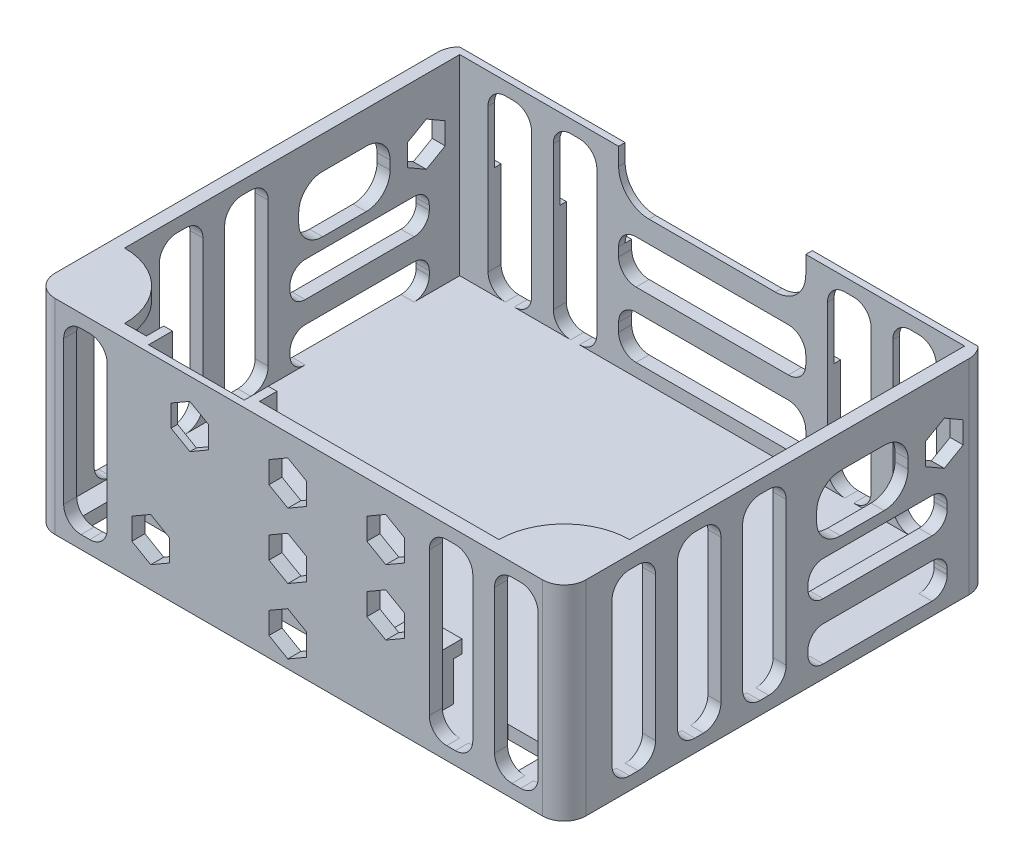
SolidWorks part; units mm, degrees
ref_plane "Front Plane" through (0, 0, 0) normal (0, 0, 1) x (1, 0, 0)
ref_plane "Top Plane" through (0, 0, 0) normal (0, 1, 0) x (1, 0, 0)
ref_plane "Right Plane" through (0, 0, 0) normal (1, 0, 0) x (0, 0, -1)
sketch "Sketch1" plane through (0, 0, 0) normal (0, 1, 0) x (1, 0, 0)
  line L1 (-81.2987, -43.7828) -> (-20.2987, -43.7828)
  line L2 (-81.2987, -43.7828) -> (-81.2987, 5.2172)
  line L3 (-81.2987, 5.2172) -> (-20.2987, 5.2172)
  line L4 (-20.2987, -43.7828) -> (-20.2987, 5.2172)
  dimension "D1" = 61
  dimension "D2" = 49
extrude "Boss-Extrude1" add sketch "Sketch1" along normal blind 23.5
sketch "Sketch2" plane through (0, 23.5, 0) normal (0, 1, 0) x (1, 0, 0)
  line L0 (-81.2987, 5.2172) -> (-81.2987, -43.7828) construction
  line L1 (-79.7987, 3.7172) -> (-21.7987, 3.7172)
  line L2 (-79.7987, 3.7172) -> (-79.7987, -42.2828)
  line L3 (-79.7987, -42.2828) -> (-21.7987, -42.2828)
  line L4 (-21.7987, 3.7172) -> (-21.7987, -42.2828)
  line L5 (-81.2987, -43.7828) -> (-20.2987, -43.7828) construction
  line L6 (-20.2987, -43.7828) -> (-20.2987, 5.2172) construction
  line L7 (-20.2987, 5.2172) -> (-81.2987, 5.2172) construction
  dimension "D1" = 1.5
  dimension "D2" = 1.5
  dimension "D3" = 1.5
  dimension "D4" = 1.5
extrude "Cut-Extrude1" cut sketch "Sketch2" against normal blind 22
sketch "Sketch3" plane through (0, 1.5, 0) normal (0, 1, 0) x (1, 0, 0)
  line L0 (-79.7987, -42.2828) -> (-21.7987, -42.2828) construction
  line L1 (-58.5387, -39.2828) -> (-42.5387, -39.2828)
  line L2 (-58.5387, -39.2828) -> (-58.5387, -42.2828)
  line L3 (-58.5387, -42.2828) -> (-42.5387, -42.2828)
  line L4 (-42.5387, -39.2828) -> (-42.5387, -42.2828)
  line L5 (-21.7987, -42.2828) -> (-21.7987, 3.7172) construction
  line L6 (-32.3987, -38.1328) -> (-27.1987, -38.1328)
  line L7 (-32.3987, -38.1328) -> (-32.3987, -42.2828)
  line L8 (-32.3987, -42.2828) -> (-27.1987, -42.2828)
  line L9 (-27.1987, -38.1328) -> (-27.1987, -42.2828)
  line L10 (-65.5387, -37.2828) -> (-77.5387, -37.2828)
  line L11 (-65.5387, -37.2828) -> (-65.5387, -42.2828)
  line L12 (-65.5387, -42.2828) -> (-77.5387, -42.2828)
  line L13 (-77.5387, -37.2828) -> (-77.5387, -42.2828)
  dimension "D1" = 3
  dimension "D2" = 5.4
  dimension "D3" = 5.2
  dimension "D4" = 10.14
  dimension "D5" = 4.15
  dimension "D6" = 7
  dimension "D7" = 12
  dimension "D8" = 16
  dimension "D9" = 5
extrude "Cut-Extrude2" cut sketch "Sketch3" against normal blind 1.5
sketch "Sketch4" plane through (0, 23.5, 0) normal (0, 1, 0) x (1, 0, 0)
  line L0 (-20.2987, 5.2172) -> (-81.2987, 5.2172) construction
  line L1 (-61.5487, 5.2172) -> (-40.0487, 5.2172)
  line L2 (-61.5487, 5.2172) -> (-61.5487, 3.7172)
  line L3 (-61.5487, 3.7172) -> (-40.0487, 3.7172)
  line L4 (-40.0487, 5.2172) -> (-40.0487, 3.7172)
  line L5 (-21.7987, 3.7172) -> (-79.7987, 3.7172) construction
  dimension "D1" = 18.25
  dimension "D2" = 18.25
extrude "Cut-Extrude3" cut sketch "Sketch4" against normal blind 5.5
sketch "Sketch5" plane through (-81.2987, 0, 0) normal (-1, 0, 0) x (0, 0, 1)
  line L0 (-5.2172, 23.5) -> (43.7828, 23.5) construction
  line L1 (4.2828, 19.75) -> (14.7828, 19.75)
  line L2 (4.2828, 19.75) -> (4.2828, 13.25)
  line L3 (4.2828, 13.25) -> (14.7828, 13.25)
  line L4 (14.7828, 19.75) -> (14.7828, 13.25)
  dimension "D1" = 10.5
  dimension "D2" = 6.5
  dimension "D3" = 3.75
  dimension "D4" = 8
extrude "Cut-Extrude6" cut sketch "Sketch5" against normal blind 61
sketch "Sketch8" plane through (0, 1.5, 0) normal (0, 1, 0) x (1, 0, 0)
  line L0 (-42.5387, -42.2828) -> (-32.3987, -42.2828) construction
  line L1 (-37.5387, -42.2828) -> (-42.5387, -42.2828)
  line L2 (-37.5387, -42.2828) -> (-37.5387, -39.2828)
  line L3 (-37.5387, -39.2828) -> (-42.5387, -39.2828)
  line L4 (-42.5387, -42.2828) -> (-42.5387, -39.2828)
  line L6 (-58.5387, -42.2828) -> (-63.5387, -42.2828)
  line L7 (-58.5387, -42.2828) -> (-58.5387, -39.2828)
  line L8 (-58.5387, -39.2828) -> (-63.5387, -39.2828)
  line L9 (-63.5387, -42.2828) -> (-63.5387, -39.2828)
  dimension "D1" = 5
  dimension "D2" = 5
extrude "Boss-Extrude2" add sketch "Sketch8" along normal blind 6
sketch "Sketch9" plane through (0, 0, 39.2828) normal (0, 0, -1) x (-1, 0, 0)
  line L0 (37.5387, 7.5) -> (42.5387, 7.5) construction
  line L1 (37.5387, 7.5) -> (42.5387, 7.5)
  line L2 (37.5387, 7.5) -> (37.5387, 6)
  line L3 (37.5387, 6) -> (42.5387, 6)
  line L4 (42.5387, 7.5) -> (42.5387, 6)
  line L5 (42.5387, 7.5) -> (42.5387, 1.5) construction
  line L6 (58.5387, 7.5) -> (63.5387, 7.5) construction
  line L7 (58.5387, 7.5) -> (63.5387, 7.5)
  line L8 (58.5387, 7.5) -> (58.5387, 6)
  line L9 (58.5387, 6) -> (63.5387, 6)
  line L10 (63.5387, 7.5) -> (63.5387, 6)
  line L11 (63.5387, 7.5) -> (63.5387, 1.5) construction
  dimension "D1" = 1.5
  dimension "D2" = 1.5
extrude "Boss-Extrude3" add sketch "Sketch9" along normal blind 1
sketch "Sketch10" plane through (0, 0, 42.2828) normal (0, 0, -1) x (-1, 0, 0)
  line L0 (79.7987, 23.5) -> (21.7987, 23.5) construction
  line L1 (57.7987, 23.5) -> (68.7987, 23.5)
  line L2 (57.7987, 23.5) -> (57.7987, 12.5)
  line L3 (57.7987, 12.5) -> (68.7987, 12.5)
  line L4 (68.7987, 23.5) -> (68.7987, 12.5)
  line L5 (79.7987, 1.5) -> (79.7987, 23.5) construction
  dimension "D1" = 11
  dimension "D2" = 11
  dimension "D3" = 0
  dimension "D4" = 11
extrude "Cut-Extrude8" cut sketch "Sketch10" against normal blind 0.75
sketch "Sketch11" plane through (0, 0, 42.2828) normal (0, 0, -1) x (-1, 0, 0)
  line L1 (57.7987, 23.5) -> (56.7987, 23.5)
  line L2 (57.7987, 23.5) -> (57.7987, 11.5)
  line L3 (57.7987, 11.5) -> (56.7987, 11.5)
  line L4 (56.7987, 23.5) -> (56.7987, 11.5)
  line L5 (68.7987, 12.5) -> (57.7987, 12.5)
  line L6 (68.7987, 12.5) -> (68.7987, 11.5)
  line L7 (68.7987, 11.5) -> (57.7987, 11.5)
  line L8 (57.7987, 12.5) -> (57.7987, 11.5)
  line L9 (68.7987, 23.5) -> (69.7987, 23.5)
  line L10 (68.7987, 23.5) -> (68.7987, 11.5)
  line L11 (68.7987, 11.5) -> (69.7987, 11.5)
  line L12 (69.7987, 23.5) -> (69.7987, 11.5)
  line M8 (68.7987, 12.5) -> (57.7987, 12.5)
  line M30 (79.7987, 23.5) -> (68.7987, 23.5)
  line M31 (68.7987, 23.5) -> (68.7987, 12.5)
  dimension "D1" = 1
  dimension "D2" = 1
  dimension "D3" = 1
  dimension "D4" = 0
extrude "Boss-Extrude4" add sketch "Sketch11" along normal blind 2 contours L7 L6 L2 M8 | L12 L6 L11 M30 M31
sketch "Sketch12" plane through (0, 23.5, 0) normal (0, 1, 0) x (1, 0, 0)
  line L1 (-21.7987, -42.2828) -> (-29.2987, -42.2828)
  line L2 (-21.7987, -42.2828) -> (-21.7987, -34.7828)
  line L3 (-21.7987, -34.7828) -> (-29.2987, -34.7828)
  line L4 (-29.2987, -42.2828) -> (-29.2987, -34.7828)
  line L5 (-79.7987, -42.2828) -> (-72.2987, -42.2828)
  line L6 (-79.7987, -42.2828) -> (-79.7987, -34.7828)
  line L7 (-79.7987, -34.7828) -> (-72.2987, -34.7828)
  line L8 (-72.2987, -42.2828) -> (-72.2987, -34.7828)
  dimension "D1" = 7.5
  dimension "D2" = 7.5
  dimension "D3" = 7.5
  dimension "D4" = 7.5
extrude "Boss-Extrude5" add sketch "Sketch12" against normal blind 1.5
fillet "Fillet1" radius 2.75 1 edges at (-80.5487, 13.25, 14.7828)
fillet "Fillet2" radius 2.75 1 edges at (-80.5487, 19.75, 14.7828)
fillet "Fillet3" radius 2.75 1 edges at (-80.5487, 19.75, 4.2828)
fillet "Fillet4" radius 2.75 1 edges at (-80.5487, 13.25, 4.2828)
fillet "Fillet5" radius 3.5 1 edges at (-40.0487, 18, -4.4672)
fillet "Fillet6" radius 3.5 1 edges at (-61.5487, 18, -4.4672)
fillet "Fillet7" radius 7.5 5 edges at (-29.2987, 22, 38.5328) (-25.5487, 22, 34.7828) (-29.2987, 22.75, 34.7828) (-25.5487, 23.5, 34.7828) (-29.2987, 23.5, 38.5328)
fillet "Fillet8" radius 7.5 5 edges at (-76.0487, 22, 34.7828) (-72.2987, 22, 38.5328) (-72.2987, 22.75, 34.7828) (-72.2987, 23.5, 38.5328) (-76.0487, 23.5, 34.7828)
fillet "Fillet9" radius 2.5 1 edges at (-20.2987, 11.75, -5.2172)
fillet "Fillet10" radius 2.5 1 edges at (-81.2987, 11.75, -5.2172)
fillet "Fillet11" radius 2.5 1 edges at (-81.2987, 11.75, 43.7828)
fillet "Fillet12" radius 2.5 1 edges at (-20.2987, 11.75, 43.7828)
sketch "Sketch13" plane through (-20.2987, 0, 0) normal (1, 0, 0) x (0, 0, -1)
  line L0 (-41.2828, 23.5) -> (2.7172, 23.5) construction
  line L1 (-36.2828, 22) -> (-35.2828, 22)
  line L2 (-38.2828, 20) -> (-38.2828, 3.5)
  line L3 (-36.2828, 1.5) -> (-35.2828, 1.5)
  line L4 (-33.2828, 20) -> (-33.2828, 3.5)
  line L5 (-28.7828, 22) -> (-27.7828, 22)
  line L6 (-30.7828, 20) -> (-30.7828, 3.5)
  line L7 (-28.7828, 1.5) -> (-27.7828, 1.5)
  line L8 (-25.7828, 20) -> (-25.7828, 3.5)
  line L9 (-21.2828, 22) -> (-20.2828, 22)
  line L10 (-23.2828, 20) -> (-23.2828, 3.5)
  line L11 (-21.2828, 1.5) -> (-20.2828, 1.5)
  line L12 (-18.2828, 20) -> (-18.2828, 3.5)
  line L17 (-41.2828, 0) -> (2.7172, 0) construction
  line L18 (-38.2828, 7.5) -> (-38.2828, 6) construction
  arc A0 (-36.2828, 22) -> (-38.2828, 20) centre (-36.2828, 20) ccw
  arc A1 (-35.2828, 22) -> (-33.2828, 20) centre (-35.2828, 20) cw
  arc A2 (-28.7828, 22) -> (-30.7828, 20) centre (-28.7828, 20) ccw
  arc A3 (-27.7828, 22) -> (-25.7828, 20) centre (-27.7828, 20) cw
  arc A4 (-21.2828, 22) -> (-23.2828, 20) centre (-21.2828, 20) ccw
  arc A5 (-20.2828, 22) -> (-18.2828, 20) centre (-20.2828, 20) cw
  arc A6 (-20.2828, 1.5) -> (-18.2828, 3.5) centre (-20.2828, 3.5) ccw
  arc A7 (-23.2828, 3.5) -> (-21.2828, 1.5) centre (-21.2828, 3.5) ccw
  arc A8 (-27.7828, 1.5) -> (-25.7828, 3.5) centre (-27.7828, 3.5) ccw
  arc A9 (-30.7828, 3.5) -> (-28.7828, 1.5) centre (-28.7828, 3.5) ccw
  arc A10 (-35.2828, 1.5) -> (-33.2828, 3.5) centre (-35.2828, 3.5) ccw
  arc A11 (-38.2828, 3.5) -> (-36.2828, 1.5) centre (-36.2828, 3.5) ccw
  point P14 (-38.2828, 22)
  point P23 (-33.2828, 22)
  point P26 (-30.7828, 22)
  point P29 (-25.7828, 22)
  point P32 (-23.2828, 22)
  point P35 (-18.2828, 22)
  dimension "D4" = 2
  dimension "D1" = 5
  dimension "D2" = 5
  dimension "D3" = 5
  dimension "D5" = 2.5
  dimension "D6" = 2.5
  dimension "D8" = 1.5
  dimension "D9" = 1.5
  dimension "D10" = 1.5
  dimension "D12" = 1.5
  dimension "D13" = 1.5
  dimension "D14" = 1.5
  dimension "D16" = 0
extrude "Cut-Extrude10" cut sketch "Sketch13" against normal blind 61
fillet "Fillet13" radius 2.75 1 edges at (-21.0487, 13.25, 14.7828)
fillet "Fillet14" radius 2.75 1 edges at (-21.0487, 19.75, 14.7828)
fillet "Fillet15" radius 2.75 1 edges at (-21.0487, 13.25, 4.2828)
fillet "Fillet16" radius 2.75 1 edges at (-21.0487, 19.75, 4.2828)
sketch "Sketch16" plane through (-20.2987, 0, 0) normal (1, 0, 0) x (0, 0, -1)
  line L0 (-4.2828, 17) -> (-4.2828, 16) construction
  line L1 (-0.1178, 19) -> (-2.2828, 17.75)
  line L2 (-2.2828, 17.75) -> (-2.2828, 15.25)
  line L3 (-2.2828, 15.25) -> (-0.1178, 14)
  line L4 (-0.1178, 14) -> (2.0473, 15.25)
  line L5 (2.0473, 15.25) -> (2.0473, 17.75)
  line L6 (2.0473, 17.75) -> (-0.1178, 19)
  circle A0 centre (-0.1178, 16.5) radius 2.1651 construction
  point P10 (-4.2828, 16.5)
  dimension "D1" = 0
  dimension "D2" = 2.5
  dimension "D3" = 2
extrude "Cut-Extrude11" cut sketch "Sketch16" against normal blind 61
sketch "Sketch19" plane through (0, 0, -5.2172) normal (0, 0, -1) x (-1, 0, 0)
  line L0 (61.5487, 23.5) -> (78.7987, 23.5) construction
  line L1 (66.0487, 22) -> (67.0487, 22)
  line L2 (64.0487, 20) -> (64.0487, 3.5)
  line L3 (66.0487, 1.5) -> (67.0487, 1.5)
  line L4 (69.0487, 20) -> (69.0487, 3.5)
  line L5 (73.5487, 22) -> (74.5487, 22)
  line L6 (71.5487, 20) -> (71.5487, 3.5)
  line L7 (73.5487, 1.5) -> (74.5487, 1.5)
  line L8 (76.5487, 20) -> (76.5487, 3.5)
  line L9 (27.0487, 22) -> (28.0487, 22)
  line L10 (25.0487, 20) -> (25.0487, 3.5)
  line L11 (27.0487, 1.5) -> (28.0487, 1.5)
  line L12 (30.0487, 20) -> (30.0487, 3.5)
  line L13 (34.5487, 22) -> (35.5487, 22)
  line L14 (32.5487, 20) -> (32.5487, 3.5)
  line L15 (34.5487, 1.5) -> (35.5487, 1.5)
  line L16 (37.5487, 20) -> (37.5487, 3.5)
  line L17 (42.0487, 15.5) -> (59.5487, 15.5)
  line L18 (40.0487, 13.5) -> (40.0487, 12.5)
  line L19 (42.0487, 10.5) -> (59.5487, 10.5)
  line L20 (61.5487, 13.5) -> (61.5487, 12.5)
  line L21 (42.0487, 8) -> (59.5487, 8)
  line L22 (40.0487, 6) -> (40.0487, 5)
  line L23 (42.0487, 3) -> (59.5487, 3)
  line L24 (61.5487, 6) -> (61.5487, 5)
  line L25 (22.7987, 0) -> (78.7987, 0) construction
  line L26 (61.5487, 21.5) -> (61.5487, 23.5) construction
  line L27 (40.0487, 21.5) -> (40.0487, 23.5) construction
  line L28 (22.7987, 23.5) -> (40.0487, 23.5) construction
  line L29 (43.5487, 18) -> (58.0487, 18) construction
  arc A0 (25.0487, 3.5) -> (27.0487, 1.5) centre (27.0487, 3.5) ccw
  arc A1 (28.0487, 1.5) -> (30.0487, 3.5) centre (28.0487, 3.5) ccw
  arc A2 (32.5487, 3.5) -> (34.5487, 1.5) centre (34.5487, 3.5) ccw
  arc A3 (35.5487, 1.5) -> (37.5487, 3.5) centre (35.5487, 3.5) ccw
  arc A4 (42.0487, 8) -> (40.0487, 6) centre (42.0487, 6) ccw
  arc A5 (40.0487, 5) -> (42.0487, 3) centre (42.0487, 5) ccw
  arc A6 (59.5487, 8) -> (61.5487, 6) centre (59.5487, 6) cw
  arc A7 (59.5487, 3) -> (61.5487, 5) centre (59.5487, 5) ccw
  arc A8 (64.0487, 3.5) -> (66.0487, 1.5) centre (66.0487, 3.5) ccw
  arc A9 (67.0487, 1.5) -> (69.0487, 3.5) centre (67.0487, 3.5) ccw
  arc A10 (71.5487, 3.5) -> (73.5487, 1.5) centre (73.5487, 3.5) ccw
  arc A11 (74.5487, 1.5) -> (76.5487, 3.5) centre (74.5487, 3.5) ccw
  arc A12 (74.5487, 22) -> (76.5487, 20) centre (74.5487, 20) cw
  arc A13 (73.5487, 22) -> (71.5487, 20) centre (73.5487, 20) ccw
  arc A14 (67.0487, 22) -> (69.0487, 20) centre (67.0487, 20) cw
  arc A15 (66.0487, 22) -> (64.0487, 20) centre (66.0487, 20) ccw
  arc A16 (59.5487, 15.5) -> (61.5487, 13.5) centre (59.5487, 13.5) cw
  arc A17 (59.5487, 10.5) -> (61.5487, 12.5) centre (59.5487, 12.5) ccw
  arc A18 (40.0487, 12.5) -> (42.0487, 10.5) centre (42.0487, 12.5) ccw
  arc A19 (42.0487, 15.5) -> (40.0487, 13.5) centre (42.0487, 13.5) ccw
  arc A20 (35.5487, 22) -> (37.5487, 20) centre (35.5487, 20) cw
  arc A21 (34.5487, 22) -> (32.5487, 20) centre (34.5487, 20) ccw
  arc A22 (28.0487, 22) -> (30.0487, 20) centre (28.0487, 20) cw
  arc A23 (27.0487, 22) -> (25.0487, 20) centre (27.0487, 20) ccw
  point P46 (40.0487, 8)
  point P49 (40.0487, 3)
  point P56 (64.0487, 1.5)
  point P59 (69.0487, 1.5)
  point P62 (71.5487, 1.5)
  point P65 (76.5487, 1.5)
  point P80 (40.0487, 10.5)
  point P83 (40.0487, 15.5)
  point P86 (37.5487, 22)
  point P89 (32.5487, 22)
  point P92 (30.0487, 22)
  point P95 (25.0487, 22)
  dimension "D25" = 2
  dimension "D1" = 1.5
  dimension "D2" = 1.5
  dimension "D3" = 5
  dimension "D4" = 5
  dimension "D5" = 2.5
  dimension "D6" = 1.5
  dimension "D7" = 1.5
  dimension "D8" = 2.5
  dimension "D9" = 2.5
  dimension "D10" = 5
  dimension "D11" = 5
  dimension "D12" = 2.5
  dimension "D13" = 1.5
  dimension "D14" = 1.5
  dimension "D15" = 1.5
  dimension "D16" = 1.5
  dimension "D17" = 2.5
  dimension "D18" = 2.5
  dimension "D19" = 2.5
  dimension "D20" = 2.5
  dimension "D21" = 5
  dimension "D22" = 5
  dimension "D23" = 2.5
  dimension "D24" = 2.5
extrude "Cut-Extrude12" cut sketch "Sketch19" against normal blind 1.5
sketch "Sketch20" plane through (-20.2987, 0, 0) normal (1, 0, 0) x (0, 0, -1)
  line L0 (-41.2828, 0) -> (2.7172, 0) construction
  line L1 (-1.5328, 1.5) -> (-14.0328, 1.5)
  line L2 (0.2172, 3.25) -> (0.2172, 3.75)
  line L3 (-1.5328, 5.5) -> (-14.0328, 5.5)
  line L4 (-15.7828, 3.25) -> (-15.7828, 3.75)
  line L5 (-1.5328, 8) -> (-14.0328, 8)
  line L6 (0.2172, 9.75) -> (0.2172, 10.25)
  line L7 (-1.5328, 12) -> (-14.0328, 12)
  line L8 (-15.7828, 9.75) -> (-15.7828, 10.25)
  line L9 (2.7172, 0) -> (2.7172, 23.5) construction
  line L10 (-18.2828, 3.5) -> (-18.2828, 20) construction
  arc A0 (-14.0328, 12) -> (-15.7828, 10.25) centre (-14.0328, 10.25) ccw
  arc A1 (-14.0328, 8) -> (-15.7828, 9.75) centre (-14.0328, 9.75) cw
  arc A2 (0.2172, 10.25) -> (-1.5328, 12) centre (-1.5328, 10.25) ccw
  arc A3 (-1.5328, 8) -> (0.2172, 9.75) centre (-1.5328, 9.75) ccw
  arc A4 (0.2172, 3.75) -> (-1.5328, 5.5) centre (-1.5328, 3.75) ccw
  arc A5 (-1.5328, 1.5) -> (0.2172, 3.25) centre (-1.5328, 3.25) ccw
  arc A6 (-14.0328, 5.5) -> (-15.7828, 3.75) centre (-14.0328, 3.75) ccw
  arc A7 (-14.0328, 1.5) -> (-15.7828, 3.25) centre (-14.0328, 3.25) cw
  point P16 (-15.7828, 12)
  point P19 (-15.7828, 8)
  point P30 (-15.7828, 5.5)
  point P33 (-15.7828, 1.5)
  dimension "D9" = 1.75
  dimension "D10" = 1.75
  dimension "D1" = 1.5
  dimension "D2" = 2.5
  dimension "D3" = 4
  dimension "D4" = 4
  dimension "D5" = 2.5
  dimension "D6" = 2.5
  dimension "D7" = 2.5
  dimension "D8" = 2.5
extrude "Cut-Extrude14" cut sketch "Sketch20" against normal blind 61
sketch "Sketch21" plane through (0, 0, 43.0328) normal (0, 0, -1) x (-1, 0, 0)
  line L1 (63.2267, 15.2845) -> (65.784, 16.7609)
  line L2 (65.784, 16.7609) -> (65.784, 19.7138)
  line L3 (65.784, 19.7138) -> (63.2267, 21.1902)
  line L4 (63.2267, 21.1902) -> (60.6695, 19.7138)
  line L5 (60.6695, 19.7138) -> (60.6695, 16.7609)
  line L6 (60.6695, 16.7609) -> (63.2267, 15.2845)
  circle A0 centre (63.2267, 18.2373) radius 2.5572 construction
sketch "Sketch22" plane through (0, 0, 42.2828) normal (0, 0, -1) x (-1, 0, 0)
  line L0 (56.7987, 23.5) -> (29.2987, 23.5) construction
  line L1 (75.7987, 22) -> (74.7987, 22)
  line L2 (77.7987, 20) -> (77.7987, 3.5)
  line L3 (75.7987, 1.5) -> (74.7987, 1.5)
  line L4 (72.7987, 20) -> (72.7987, 3.5)
  line L5 (26.2987, 22) -> (25.2987, 22)
  line L6 (28.2987, 20) -> (28.2987, 3.5)
  line L7 (26.2987, 1.5) -> (25.2987, 1.5)
  line L8 (23.2987, 20) -> (23.2987, 3.5)
  line L9 (33.7987, 22) -> (32.7987, 22)
  line L10 (35.7987, 20) -> (35.7987, 3.5)
  line L11 (33.7987, 1.5) -> (32.7987, 1.5)
  line L12 (30.7987, 20) -> (30.7987, 3.5)
  line L13 (78.7987, 23.5) -> (22.7987, 23.5) construction
  line L14 (27.1987, 1.5) -> (21.7987, 1.5) construction
  line L15 (37.5387, 1.5) -> (32.3987, 1.5) construction
  line L16 (21.7987, 1.5) -> (21.7987, 22) construction
  line L17 (79.7987, 1.5) -> (79.7987, 22) construction
  line L18 (79.7987, 1.5) -> (77.5387, 1.5) construction
  arc A0 (32.7987, 1.5) -> (30.7987, 3.5) centre (32.7987, 3.5) cw
  arc A1 (25.2987, 1.5) -> (23.2987, 3.5) centre (25.2987, 3.5) cw
  arc A2 (25.2987, 22) -> (23.2987, 20) centre (25.2987, 20) ccw
  arc A3 (33.7987, 22) -> (35.7987, 20) centre (33.7987, 20) cw
  arc A4 (32.7987, 22) -> (30.7987, 20) centre (32.7987, 20) ccw
  arc A5 (26.2987, 22) -> (28.2987, 20) centre (26.2987, 20) cw
  arc A6 (28.2987, 3.5) -> (26.2987, 1.5) centre (26.2987, 3.5) cw
  arc A7 (35.7987, 3.5) -> (33.7987, 1.5) centre (33.7987, 3.5) cw
  arc A8 (75.7987, 22) -> (77.7987, 20) centre (75.7987, 20) cw
  arc A9 (74.7987, 22) -> (72.7987, 20) centre (74.7987, 20) ccw
  arc A10 (74.7987, 1.5) -> (72.7987, 3.5) centre (74.7987, 3.5) cw
  arc A11 (77.7987, 3.5) -> (75.7987, 1.5) centre (75.7987, 3.5) cw
  point P28 (30.7987, 1.5)
  point P31 (23.2987, 1.5)
  point P42 (28.2987, 1.5)
  point P45 (35.7987, 1.5)
  point P48 (77.7987, 22)
  point P51 (72.7987, 22)
  dimension "D13" = 2
  dimension "D1" = 1.5
  dimension "D2" = 1.5
  dimension "D3" = 0
  dimension "D4" = 0
  dimension "D5" = 5
  dimension "D6" = 5
  dimension "D7" = 1.5
  dimension "D8" = 2.5
  dimension "D9" = 5
  dimension "D10" = 1.5
  dimension "D11" = 2
  dimension "D12" = 0
extrude "Cut-Extrude15" cut sketch "Sketch22" against normal blind 1.5
sketch "Sketch23" plane through (0, 0, 43.0328) normal (0, 0, -1) x (-1, 0, 0)
  line L0 (56.7987, 23.5) -> (29.2987, 23.5) construction
  line L1 (40.7987, 16) -> (42.9638, 17.25)
  line L2 (42.9638, 17.25) -> (42.9638, 19.75)
  line L3 (42.9638, 19.75) -> (40.7987, 21)
  line L4 (40.7987, 21) -> (38.6336, 19.75)
  line L5 (38.6336, 19.75) -> (38.6336, 17.25)
  line L6 (38.6336, 17.25) -> (40.7987, 16)
  line L7 (35.7987, 3.5) -> (35.7987, 20) construction
  line L8 (52.0487, 16) -> (54.2138, 17.25)
  line L9 (54.2138, 17.25) -> (54.2138, 19.75)
  line L10 (54.2138, 19.75) -> (52.0487, 21)
  line L11 (52.0487, 21) -> (49.8836, 19.75)
  line L12 (49.8836, 19.75) -> (49.8836, 17.25)
  line L13 (49.8836, 17.25) -> (52.0487, 16)
  line L14 (63.2987, 16) -> (65.4638, 17.25)
  line L15 (65.4638, 17.25) -> (65.4638, 19.75)
  line L16 (65.4638, 19.75) -> (63.2987, 21)
  line L17 (63.2987, 21) -> (61.1336, 19.75)
  line L18 (61.1336, 19.75) -> (61.1336, 17.25)
  line L19 (61.1336, 17.25) -> (63.2987, 16)
  line L20 (52.0487, 8.5) -> (54.2138, 9.75)
  line L21 (54.2138, 9.75) -> (54.2138, 12.25)
  line L22 (54.2138, 12.25) -> (52.0487, 13.5)
  line L23 (52.0487, 13.5) -> (49.8836, 12.25)
  line L24 (49.8836, 12.25) -> (49.8836, 9.75)
  line L25 (49.8836, 9.75) -> (52.0487, 8.5)
  line L32 (52.0487, 1) -> (54.2138, 2.25)
  line L33 (54.2138, 2.25) -> (54.2138, 4.75)
  line L34 (54.2138, 4.75) -> (52.0487, 6)
  line L35 (52.0487, 6) -> (49.8836, 4.75)
  line L36 (49.8836, 4.75) -> (49.8836, 2.25)
  line L37 (49.8836, 2.25) -> (52.0487, 1)
  line L44 (40.7987, 8.5) -> (42.9638, 9.75)
  line L45 (42.9638, 9.75) -> (42.9638, 12.25)
  line L46 (42.9638, 12.25) -> (40.7987, 13.5)
  line L47 (40.7987, 13.5) -> (38.6336, 12.25)
  line L48 (38.6336, 12.25) -> (38.6336, 9.75)
  line L49 (38.6336, 9.75) -> (40.7987, 8.5)
  line L56 (42.9638, 4.75) -> (40.7987, 6) [skipped]
  line L57 (40.7987, 6) -> (38.6336, 4.75) [skipped]
  line L58 (38.6336, 4.75) -> (38.6336, 2.25) [skipped]
  line L59 (38.6336, 2.25) -> (40.7987, 1) [skipped]
  line L60 (40.7987, 1) -> (42.9638, 2.25) [skipped]
  line L61 (42.9638, 2.25) -> (42.9638, 4.75) [skipped]
  line L62 (63.2987, 13.5) -> (61.1336, 12.25) [skipped]
  line L63 (65.4638, 12.25) -> (63.2987, 13.5) [skipped]
  line L64 (65.4638, 9.75) -> (65.4638, 12.25) [skipped]
  line L65 (63.2987, 8.5) -> (65.4638, 9.75) [skipped]
  line L66 (61.1336, 9.75) -> (63.2987, 8.5) [skipped]
  line L67 (61.1336, 12.25) -> (61.1336, 9.75) [skipped]
  line L68 (65.4638, 4.75) -> (63.2987, 6) [skipped]
  line L69 (63.2987, 6) -> (61.1336, 4.75) [skipped]
  line L70 (61.1336, 4.75) -> (61.1336, 2.25) [skipped]
  line L71 (61.1336, 2.25) -> (63.2987, 1) [skipped]
  line L72 (63.2987, 1) -> (65.4638, 2.25) [skipped]
  line L73 (65.4638, 2.25) -> (65.4638, 4.75) [skipped]
  circle A0 centre (40.7987, 18.5) radius 2.1651 construction
  dimension "D1" = 2.5
  dimension "D2" = 5
  dimension "D3" = 5
  dimension "D4" = 3
  dimension "D5" = 3
extrude "Cut-Extrude18" cut sketch "Sketch23" against normal blind 1.5 and the other way blind 1.5
sketch "Sketch24" plane through (0, 0, 42.2828) normal (0, 0, -1) x (-1, 0, 0)
  line L0 (77.5387, 0) -> (65.5387, 0) construction
  line L1 (67.7987, 7.5) -> (65.6336, 6.25)
  line L2 (65.6336, 6.25) -> (65.6336, 3.75)
  line L3 (65.6336, 3.75) -> (67.7987, 2.5)
  line L4 (67.7987, 2.5) -> (69.9638, 3.75)
  line L5 (69.9638, 3.75) -> (69.9638, 6.25)
  line L6 (69.9638, 6.25) -> (67.7987, 7.5)
  line L7 (72.7987, 20) -> (72.7987, 3.5) construction
  circle A0 centre (67.7987, 5) radius 2.1651 construction
  dimension "D1" = 2.5
  dimension "D2" = 5
  dimension "D3" = 5
extrude "Cut-Extrude19" cut sketch "Sketch24" against normal blind 1.5
sketch "Sketch25" plane through (0, 0, -5.2172) normal (0, 0, -1) x (-1, 0, 0)
  line L0 (22.7987, 23.5) -> (40.0487, 23.5) construction
  line L1 (20.2987, 23.5) -> (81.2987, 23.5)
  line L2 (20.2987, 23.5) -> (20.2987, 13.5)
  line L3 (20.2987, 13.5) -> (81.2987, 13.5)
  line L4 (81.2987, 23.5) -> (81.2987, 13.5)
  line L5 (81.2987, 23.5) -> (81.2987, 0) construction
  dimension "D1" = 0
  dimension "D2" = 0
  dimension "D3" = 10
extrude "Cut-Extrude20" cut sketch "Sketch25" against normal blind 0.75
